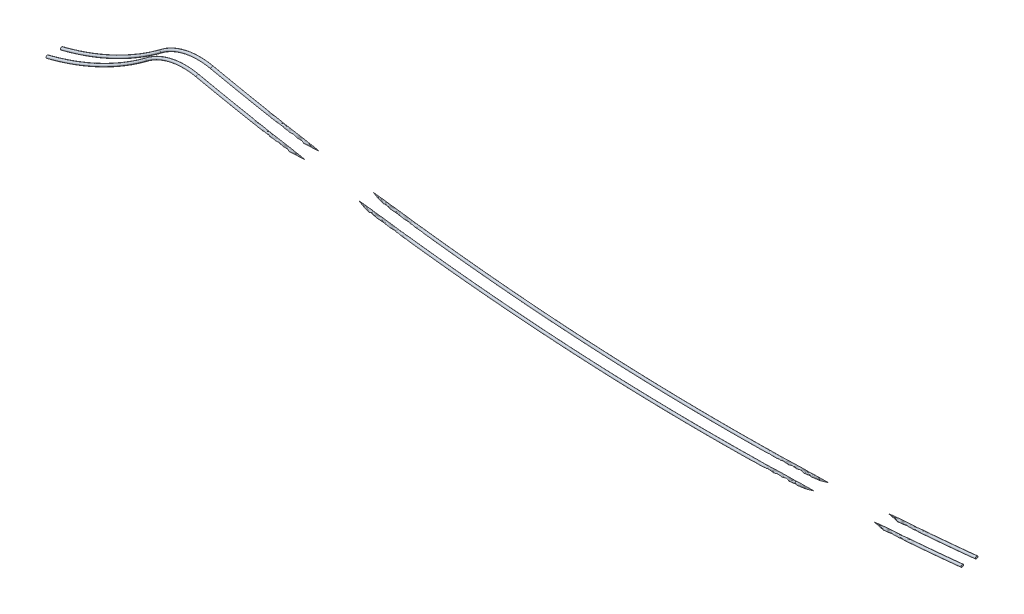
SolidWorks part; units mm, degrees
ref_plane "前基準面" through (0, 0, 0) normal (0, 0, 1) x (1, 0, 0)
ref_plane "上基準面" through (0, 0, 0) normal (0, 1, 0) x (1, 0, 0)
ref_plane "右基準面" through (0, 0, 0) normal (1, 0, 0) x (0, 0, -1)
sketch "草圖1" plane through (0, 0, 0) normal (0, 0, 1) x (1, 0, 0)
  line L1 (0, 0) -> (500, 0) construction
  line L2 (0, 0) -> (0, 120.8101) construction
  line L3 (0, 120.8101) -> (500, 120.8101) construction
  line L4 (500, 0) -> (500, 120.8101) construction
  arc A0 (0, 0) -> (55.5524, 26.4563) centre (-38.2274, 151.8209) ccw
  arc A1 (55.5524, 26.4563) -> (83.4894, 32.5697) centre (76.242, -1.2016) cw
  arc A2 (83.4894, 32.5697) -> (508.7698, 9.1823) centre (370.2586, 1368.8536) ccw
  point P8 (508.7698, 9.1823)
  point P9 (0, 0)
  point P10 (0, 0)
  point P11 (0, 0)
  point P15 (0, 0)
  point P16 (0, 0)
  point P17 (0, 0)
  point P18 (0, 0)
  dimension "D1" = 500
sketch "草圖2" plane through (0, 0, 0) normal (1, 0, 0) x (0, 0, -1)
  line L0 (4, 0) -> (-4, 0) construction
  circle A0 centre (-4, 0) radius 0.75
  circle A1 centre (4, 0) radius 0.75
  point P4 (0, 0)
  dimension "D1" = 1.5
  dimension "D2" = 8
sweep "掃出1" add profiles "草圖2" path "草圖1"
